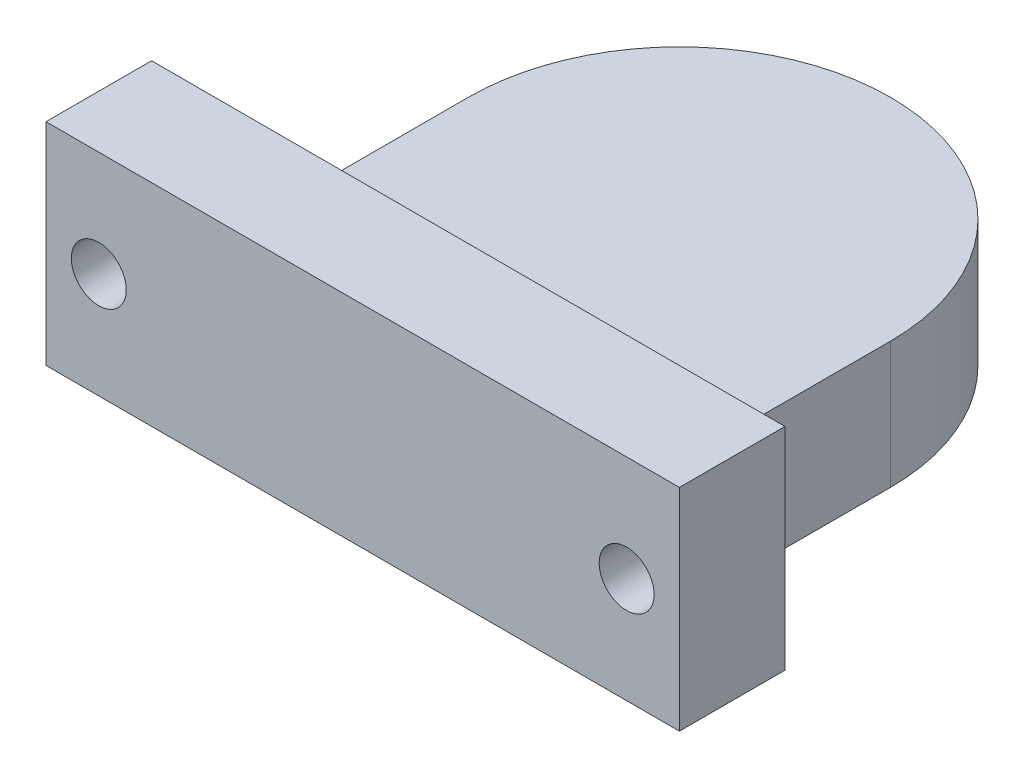
SolidWorks part; units mm, degrees
material "PET"
ref_plane "Front Plane" through (0, 0, 0) normal (0, 0, 1) x (1, 0, 0)
ref_plane "Top Plane" through (0, 0, 0) normal (0, 1, 0) x (1, 0, 0)
ref_plane "Right Plane" through (0, 0, 0) normal (1, 0, 0) x (0, 0, -1)
sketch "Sketch1" plane through (0, 0, 0) normal (0, 1, 0) x (1, 0, 0)
  line L5 (-20, 0) -> (-20, -20)
  line L6 (20, 0) -> (20, -20)
  line L9 (-20, -20) -> (20, -20)
  circle A0 centre (0, 0) radius 11.1
  arc A1 (20, 0) -> (-20, 0) centre (0, 0) ccw
  dimension "D1" = 22.2
  dimension "D2" = 40
  dimension "D3" = 20
extrude "Boss-Extrude1" add sketch "Sketch1" along normal blind 12
sketch "Sketch3" plane through (0, 12, 0) normal (0, 1, 0) x (1, 0, 0)
  circle A0 centre (0, 0) radius 11.1
  circle A1 centre (0, 0) radius 11.1 construction
extrude "Boss-Extrude2" add sketch "Sketch3" against normal blind 2
sketch "Sketch4" plane through (0, 0, 0) normal (0, 1, 0) x (1, 0, 0)
  line L0 (-20, -20) -> (20, -20) construction
  line L1 (-30, -20) -> (30, -20)
  line L2 (-30, -20) -> (-30, -30)
  line L3 (-30, -30) -> (30, -30)
  line L4 (30, -20) -> (30, -30)
  point P6 (0, -20)
  dimension "D1" = 10
  dimension "D2" = 60
extrude "Boss-Extrude3" add sketch "Sketch4" along normal blind 20
sketch "Sketch5" plane through (0, 0, 20) normal (0, 0, -1) x (-1, 0, 0)
  line L0 (-30, 10) -> (30, 10) construction
  line L1 (-30, 20) -> (-30, 0) construction
  line L2 (30, 20) -> (30, 0) construction
  line L3 (-20, 12) -> (-20, 0) construction
  line L4 (20, 12) -> (20, 0) construction
  circle A0 centre (25, 10) radius 2.6
  circle A1 centre (-25, 10) radius 2.6
  dimension "D1" = 5.2
  dimension "D2" = 5.2
  dimension "D3" = 5
  dimension "D4" = 5
  dimension "D5" = 5
  dimension "D6" = 5
extrude "Cut-Extrude1" cut sketch "Sketch5" against normal through all
equation "\"tolerance\"= 0.2"
equation "\"D1@Sketch1\"=\"tolerance\"+22"
